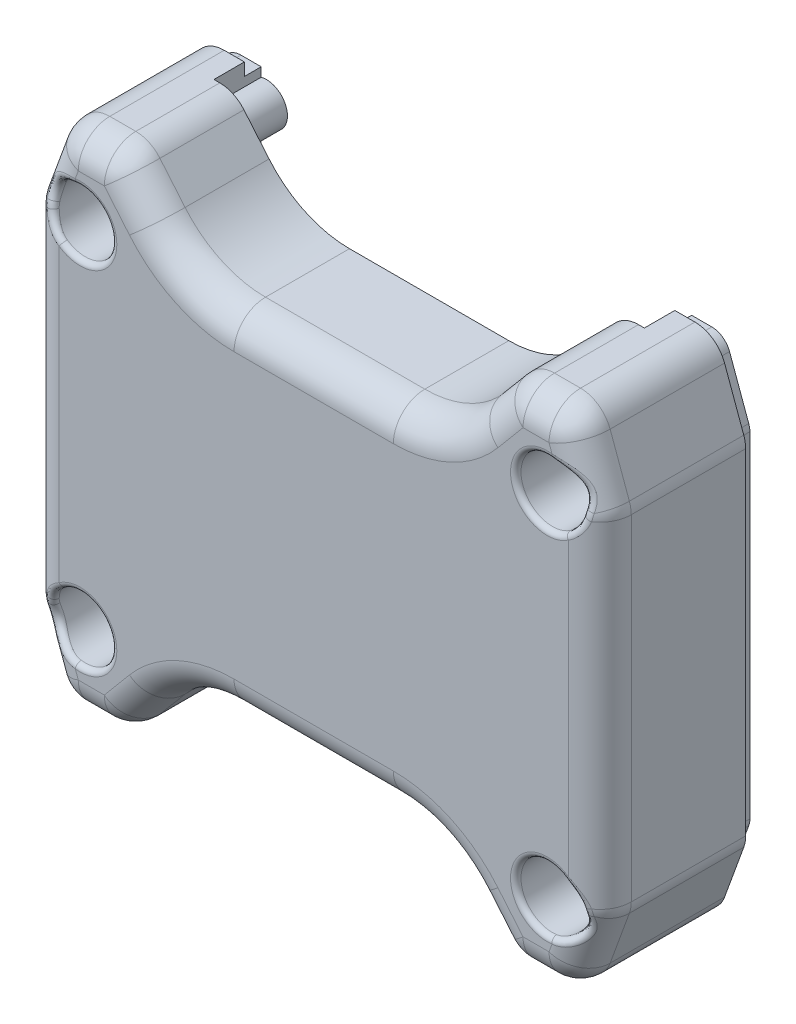
SolidWorks part; units mm, degrees
ref_plane "Alzado" through (0, 0, 0) normal (0, 0, 1) x (1, 0, 0)
ref_plane "Planta" through (0, 0, 0) normal (0, 1, 0) x (1, 0, 0)
ref_plane "Vista lateral" through (0, 0, 0) normal (1, 0, 0) x (0, 0, -1)
sketch "Croquis2" plane through (0, 0, 0) normal (0, 0, 1) x (1, 0, 0)
  line L0 (-20, 7.75) -> (-20, 15.75)
  line L1 (-20, -41.25) -> (20, -41.25)
  line L2 (-20, -41.25) -> (-20, -24.25)
  line L3 (-20, 38.75) -> (20, 38.75)
  line L4 (20, -41.25) -> (20, -24.25)
  line L5 (-20, 7.75) -> (5, 7.75)
  line L6 (-20, 4.75) -> (5, 4.75)
  line L7 (5, 7.75) -> (5, 4.75)
  line L8 (20, -10.25) -> (-5, -10.25)
  line L9 (20, -7.25) -> (-5, -7.25)
  line L10 (-5, -10.25) -> (-5, -7.25)
  line L11 (20, -7.25) -> (20, 15.75)
  line L12 (0, 38.75) -> (0, -41.25) construction
  line L14 (-20, 21.75) -> (-20, 38.75)
  line L15 (20, 21.75) -> (20, 38.75)
  line L16 (-20, -21.25) -> (20, -21.25) construction
  line L17 (-20, -18.25) -> (-20, 4.75)
  line L18 (20, -18.25) -> (20, -10.25)
  line L19 (0, 15.25) -> (0, -17.75) construction
  line L24 (27.25, -1.25) -> (-27.25, -1.25) construction
  line L29 (0, 15.25) -> (0, -17.75) construction
  line L39 (22.4196, 22.75) -> (21, 22.75)
  line L40 (21, 22.75) -> (21, 21.75)
  line L41 (21, 21.75) -> (22.4196, 21.75)
  line L42 (24.299, 20.434) -> (26.25, 15.0737)
  line L43 (26.25, 15.0737) -> (26.25, -17.5737)
  line L44 (26.25, -17.5737) -> (24.299, -22.934)
  line L45 (22.4196, -24.25) -> (21, -24.25)
  line L46 (21, -24.25) -> (21, -25.25)
  line L47 (21, -25.25) -> (22.4196, -25.25)
  line L48 (25.2387, -23.2761) -> (27.0691, -18.2471)
  line L49 (27.25, -17.221) -> (27.25, 14.721)
  line L50 (27.0691, 15.7471) -> (25.2387, 20.7761)
  line L51 (-22.4196, -25.25) -> (-21, -25.25)
  line L52 (-21, -25.25) -> (-21, -24.25)
  line L53 (-21, -24.25) -> (-22.4196, -24.25)
  line L54 (-24.299, -22.934) -> (-26.25, -17.5737)
  line L55 (-26.25, -17.5737) -> (-26.25, 15.0737)
  line L56 (-26.25, 15.0737) -> (-24.299, 20.434)
  line L57 (-22.4196, 21.75) -> (-21, 21.75)
  line L58 (-21, 21.75) -> (-21, 22.75)
  line L59 (-21, 22.75) -> (-22.4196, 22.75)
  line L60 (-25.2387, 20.7761) -> (-27.0691, 15.7471)
  line L61 (-27.25, 14.721) -> (-27.25, -17.221)
  line L62 (-27.0691, -18.2471) -> (-25.2387, -23.2761)
  line L63 (-21, 22.75) -> (-21, 21.75)
  line L64 (-21, 21.75) -> (-22.4196, 21.75)
  line L65 (-24.299, 20.434) -> (-26.25, 15.0737)
  line L66 (-26.25, 15.0737) -> (-26.25, -17.5737)
  line L67 (-26.25, -17.5737) -> (-24.299, -22.934)
  line L68 (-22.4196, -24.25) -> (-21, -24.25)
  line L69 (-21, -24.25) -> (-21, -25.25)
  line L70 (-21, -25.25) -> (-19.9422, -25.25)
  line L71 (-17.644, -24.1784) -> (-15.2474, -21.3221)
  line L72 (-7.5869, -17.75) -> (7.5869, -17.75)
  line L73 (15.2474, -21.3221) -> (17.644, -24.1784)
  line L74 (19.9422, -25.25) -> (21, -25.25)
  line L75 (21, -25.25) -> (21, -24.25)
  line L76 (21, -24.25) -> (22.4196, -24.25)
  line L77 (24.299, -22.934) -> (26.25, -17.5737)
  line L78 (26.25, -17.5737) -> (26.25, 15.0737)
  line L79 (26.25, 15.0737) -> (24.299, 20.434)
  line L80 (22.4196, 21.75) -> (21, 21.75)
  line L81 (21, 21.75) -> (21, 22.75)
  line L82 (21, 22.75) -> (19.9422, 22.75)
  line L83 (17.644, 21.6784) -> (15.2474, 18.8221)
  line L84 (7.5869, 15.25) -> (-7.5869, 15.25)
  line L85 (-15.2474, 18.8221) -> (-17.644, 21.6784)
  line L86 (-19.9422, 22.75) -> (-21, 22.75)
  line L87 (-20, -41.25) -> (20, -41.25)
  line L88 (-20, -41.25) -> (-20, -24.25)
  line L89 (-5, -10.25) -> (-5, -7.25)
  line L90 (20, -7.25) -> (-5, -7.25)
  line L91 (20, -10.25) -> (-5, -10.25)
  line L92 (5, 7.75) -> (5, 4.75)
  line L93 (-20, 4.75) -> (5, 4.75)
  line L94 (-20, 7.75) -> (5, 7.75)
  line L95 (-20, 7.75) -> (-20, 15.75)
  line L96 (20, -7.25) -> (20, 15.75)
  line L97 (20, -18.25) -> (20, -10.25)
  line L98 (20, -41.25) -> (20, -24.25)
  line L99 (-20, -18.25) -> (-20, 4.75)
  line L100 (-20, 21.75) -> (-20, 38.75)
  line L101 (-20, 38.75) -> (20, 38.75)
  line L102 (20, 21.75) -> (20, 38.75)
  line L103 (-27.0691, -18.2471) -> (-25.2387, -23.2761)
  line L104 (-27.25, 14.721) -> (-27.25, -17.221)
  line L105 (-25.2387, 20.7761) -> (-27.0691, 15.7471)
  line L106 (-21, 21.75) -> (-22.4196, 21.75)
  line L107 (-22.4196, -24.25) -> (-21, -24.25)
  line L108 (-21, -24.25) -> (-21, -25.25)
  line L109 (-21, 22.75) -> (-21, 21.75)
  line L110 (-26.25, 15.0737) -> (-26.25, -17.5737)
  line L111 (-24.299, 20.434) -> (-26.25, 15.0737)
  line L112 (-19.9422, 22.75) -> (-22.4196, 22.75)
  line L113 (-22.4196, -25.25) -> (-19.9422, -25.25)
  line L114 (-26.25, -17.5737) -> (-24.299, -22.934)
  line L115 (27.0691, 15.7471) -> (25.2387, 20.7761)
  line L116 (27.25, -17.221) -> (27.25, 14.721)
  line L117 (25.2387, -23.2761) -> (27.0691, -18.2471)
  line L118 (21, -24.25) -> (22.4196, -24.25)
  line L119 (26.25, 15.0737) -> (24.299, 20.434)
  line L120 (22.4196, 21.75) -> (21, 21.75)
  line L121 (21, 21.75) -> (21, 22.75)
  line L122 (21, -25.25) -> (21, -24.25)
  line L123 (22.4196, 22.75) -> (19.9422, 22.75)
  line L124 (26.25, -17.5737) -> (26.25, 15.0737)
  line L125 (24.299, -22.934) -> (26.25, -17.5737)
  line L126 (19.9422, -25.25) -> (22.4196, -25.25)
  line L127 (-17.644, 21.6784) -> (-15.2474, 18.8221)
  line L128 (7.5869, 15.25) -> (-7.5869, 15.25)
  line L129 (15.2474, 18.8221) -> (17.644, 21.6784)
  line L130 (17.644, -24.1784) -> (15.2474, -21.3221)
  line L131 (-7.5869, -17.75) -> (7.5869, -17.75)
  line L132 (-15.2474, -21.3221) -> (-17.644, -24.1784)
  line L133 (-25.25, 13.75) -> (-24.6867, 13.75)
  line L134 (19.8133, -16.25) -> (-19.8133, -16.25)
  line L135 (-19.8133, 13.75) -> (19.8133, 13.75)
  line L136 (24.6867, 13.75) -> (25.25, 13.75)
  line L137 (25.25, -16.25) -> (24.6867, -16.25)
  line L138 (-25.25, -16.25) -> (-25.25, 13.75)
  line L139 (-24.6867, -16.25) -> (-25.25, -16.25)
  line L140 (25.25, 13.75) -> (25.25, -16.25)
  line L141 (-25.25, -14) -> (-17.25, -14)
  line L142 (-17.25, -13) -> (-17.25, -16)
  line L143 (-17.25, -16) -> (-20.0139, -16)
  line L144 (-24.4861, -16) -> (-25.25, -16)
  line L145 (20.0139, -16) -> (17.25, -16)
  line L146 (17.25, -14) -> (25.25, -14)
  line L147 (17.25, -16) -> (17.25, -14)
  line L148 (25.25, -16) -> (24.4861, -16)
  line L149 (25.25, 11.5) -> (17.25, 11.5)
  line L150 (17.25, 13.5) -> (20.0139, 13.5)
  line L151 (17.25, 11.5) -> (17.25, 13.5)
  line L152 (24.4861, 13.5) -> (25.25, 13.5)
  line L153 (-17.25, 13.5) -> (-17.25, 10.5)
  line L154 (-20.0139, 13.5) -> (-17.25, 13.5)
  line L155 (-25.25, 13.5) -> (-24.4861, 13.5)
  line L156 (-17.25, 11.5) -> (-25.25, 11.5)
  line L157 (-24.25, 10.5) -> (-24.25, 6.5)
  line L158 (-24.25, 6.5) -> (-25.25, 6.5)
  line L159 (-17.25, 10.5) -> (-24.25, 10.5)
  line L160 (19.75, -13) -> (19.75, -14)
  line L161 (24.25, -13) -> (24.25, -9)
  line L162 (25.25, -9) -> (24.25, -9)
  line L163 (19.75, -13) -> (24.25, -13)
  line L164 (-24.25, -9) -> (-24.25, -13)
  line L165 (-24.25, -13) -> (-17.25, -13)
  line L166 (-25.25, -9) -> (-24.25, -9)
  line L167 (24.9375, 0.5) -> (24.9375, 2.5)
  line L168 (16, 13.75) -> (16, -16.25)
  line L169 (24.9375, 2.5) -> (25.25, 2.5)
  line L170 (-16, -16.25) -> (-16, 13.75)
  line L171 (24.9375, 0.5) -> (21.25, 0.5)
  line L172 (21.25, 0.5) -> (21.25, 11.5)
  line L173 (13.5, -11.25) -> (13.5, -6.25)
  line L174 (13.5, -6.25) -> (15.5, -6.25)
  line L175 (15.5, -6.25) -> (15.5, -13.25)
  line L176 (15.5, -13.25) -> (8, -13.25)
  line L177 (8, -13.25) -> (8, -11.25)
  line L178 (8, -11.25) -> (13.5, -11.25)
  line L179 (-13.5, 3.25) -> (-15.5, 3.25)
  line L180 (-15.5, 3.25) -> (-15.5, 10.25)
  line L181 (-15.5, 10.25) -> (-8, 10.25)
  line L182 (-8, 10.25) -> (-8, 8.25)
  line L183 (-8, 8.25) -> (-13.5, 8.25)
  line L184 (-13.5, 8.25) -> (-13.5, 3.25)
  line L185 (-13.5, -11.25) -> (-8, -11.25)
  line L186 (-8, -11.25) -> (-8, -13.25)
  line L187 (-8, -13.25) -> (-15.5, -13.25)
  line L188 (-15.5, -13.25) -> (-15.5, -6.25)
  line L189 (-15.5, -6.25) -> (-13.5, -6.25)
  line L190 (-13.5, -6.25) -> (-13.5, -11.25)
  line L191 (8, 10.25) -> (15.5, 10.25)
  line L192 (13.5, 3.25) -> (13.5, 8.25)
  line L193 (13.5, 8.25) -> (8, 8.25)
  line L194 (8, 8.25) -> (8, 10.25)
  line L195 (15.5, 10.25) -> (15.5, 3.25)
  line L196 (15.5, 3.25) -> (13.5, 3.25)
  line L197 (-12.5, -3.75) -> (-12.5, 4.625)
  line L198 (10.5, -5.75) -> (-10.5, -5.75)
  line L199 (12.5, 4.625) -> (12.5, -3.75)
  line L200 (-10.5, 6.625) -> (10.5, 6.625)
  circle A0 centre (0, 24.75) radius 8
  circle A1 centre (0, -27.25) radius 8
  arc A2 (-20, 15.75) -> (-20, 21.75) centre (-20, 18.75) ccw
  arc A3 (20, 21.75) -> (20, 15.75) centre (20, 18.75) ccw
  arc A4 (-20, -24.25) -> (-20, -18.25) centre (-20, -21.25) ccw
  arc A5 (20, -18.25) -> (20, -24.25) centre (20, -21.25) ccw
  circle A6 centre (-20, 18.75) radius 2
  circle A7 centre (20, 18.75) radius 2
  circle A8 centre (20, -21.25) radius 2
  circle A9 centre (-20, -21.25) radius 2
  circle A10 centre (-22.25, -18) radius 1.5
  circle A11 centre (-22.25, -18) radius 3
  circle A12 centre (20, -21.25) radius 2
  circle A13 centre (22.25, -18) radius 1.5
  circle A14 centre (22.25, -18) radius 3
  circle A15 centre (22.25, 15.5) radius 3
  circle A16 centre (22.25, 15.5) radius 1.5
  circle A17 centre (-22.25, 15.5) radius 3
  circle A18 centre (-22.25, 15.5) radius 1.5
  arc A19 (24.299, 20.434) -> (22.4196, 21.75) centre (22.4196, 19.75) ccw
  arc A20 (22.4196, -24.25) -> (24.299, -22.934) centre (22.4196, -22.25) ccw
  arc A21 (22.4196, -25.25) -> (25.2387, -23.2761) centre (22.4196, -22.25) ccw
  arc A22 (27.0691, -18.2471) -> (27.25, -17.221) centre (24.25, -17.221) ccw
  arc A23 (27.25, 14.721) -> (27.0691, 15.7471) centre (24.25, 14.721) ccw
  arc A24 (25.2387, 20.7761) -> (22.4196, 22.75) centre (22.4196, 19.75) ccw
  arc A25 (-24.299, -22.934) -> (-22.4196, -24.25) centre (-22.4196, -22.25) ccw
  arc A26 (-22.4196, 21.75) -> (-24.299, 20.434) centre (-22.4196, 19.75) ccw
  arc A27 (-22.4196, 22.75) -> (-25.2387, 20.7761) centre (-22.4196, 19.75) ccw
  arc A28 (-27.0691, 15.7471) -> (-27.25, 14.721) centre (-24.25, 14.721) ccw
  arc A29 (-27.25, -17.221) -> (-27.0691, -18.2471) centre (-24.25, -17.221) ccw
  arc A30 (-25.2387, -23.2761) -> (-22.4196, -25.25) centre (-22.4196, -22.25) ccw
  arc A31 (-22.4196, 21.75) -> (-24.299, 20.434) centre (-22.4196, 19.75) ccw
  arc A32 (-24.299, -22.934) -> (-22.4196, -24.25) centre (-22.4196, -22.25) ccw
  arc A33 (-19.9422, -25.25) -> (-17.644, -24.1784) centre (-19.9422, -22.25) ccw
  arc A34 (-7.5869, -17.75) -> (-15.2474, -21.3221) centre (-7.5869, -27.75) ccw
  arc A35 (15.2474, -21.3221) -> (7.5869, -17.75) centre (7.5869, -27.75) ccw
  arc A36 (17.644, -24.1784) -> (19.9422, -25.25) centre (19.9422, -22.25) ccw
  arc A37 (22.4196, -24.25) -> (24.299, -22.934) centre (22.4196, -22.25) ccw
  arc A38 (24.299, 20.434) -> (22.4196, 21.75) centre (22.4196, 19.75) ccw
  arc A39 (19.9422, 22.75) -> (17.644, 21.6784) centre (19.9422, 19.75) ccw
  arc A40 (7.5869, 15.25) -> (15.2474, 18.8221) centre (7.5869, 25.25) ccw
  arc A41 (-15.2474, 18.8221) -> (-7.5869, 15.25) centre (-7.5869, 25.25) ccw
  arc A42 (-17.644, 21.6784) -> (-19.9422, 22.75) centre (-19.9422, 19.75) ccw
  circle A43 centre (0, -27.25) radius 8
  circle A44 centre (0, 24.75) radius 8
  arc A45 (-20, 15.75) -> (-20, 21.75) centre (-20, 18.75) ccw
  arc A46 (20, -18.25) -> (20, -24.25) centre (20, -21.25) ccw
  arc A47 (-20, -24.25) -> (-20, -18.25) centre (-20, -21.25) ccw
  arc A48 (20, 21.75) -> (20, 15.75) centre (20, 18.75) ccw
  circle A49 centre (-20, -21.25) radius 2
  circle A50 centre (20, -21.25) radius 2
  circle A51 centre (20, 18.75) radius 2
  circle A52 centre (-20, 18.75) radius 2
  circle A53 centre (22.25, 15.5) radius 1.5
  circle A54 centre (22.25, -18) radius 1.5
  circle A55 centre (-22.25, -18) radius 1.5
  circle A56 centre (-22.25, 15.5) radius 1.5
  arc A57 (-22.4196, 22.75) -> (-25.2387, 20.7761) centre (-22.4196, 19.75) ccw
  arc A58 (-24.299, -22.934) -> (-22.4196, -24.25) centre (-22.4196, -22.25) ccw
  arc A59 (-27.25, -17.221) -> (-27.0691, -18.2471) centre (-24.25, -17.221) ccw
  arc A60 (-25.2387, -23.2761) -> (-22.4196, -25.25) centre (-22.4196, -22.25) ccw
  arc A61 (-27.0691, 15.7471) -> (-27.25, 14.721) centre (-24.25, 14.721) ccw
  arc A62 (-22.4196, 21.75) -> (-24.299, 20.434) centre (-22.4196, 19.75) ccw
  arc A63 (27.25, 14.721) -> (27.0691, 15.7471) centre (24.25, 14.721) ccw
  arc A64 (27.0691, -18.2471) -> (27.25, -17.221) centre (24.25, -17.221) ccw
  arc A65 (22.4196, -24.25) -> (24.299, -22.934) centre (22.4196, -22.25) ccw
  arc A66 (24.299, 20.434) -> (22.4196, 21.75) centre (22.4196, 19.75) ccw
  arc A67 (25.2387, 20.7761) -> (22.4196, 22.75) centre (22.4196, 19.75) ccw
  arc A68 (22.4196, -25.25) -> (25.2387, -23.2761) centre (22.4196, -22.25) ccw
  arc A69 (-17.644, 21.6784) -> (-19.9422, 22.75) centre (-19.9422, 19.75) ccw
  arc A70 (-15.2474, 18.8221) -> (-7.5869, 15.25) centre (-7.5869, 25.25) ccw
  arc A71 (7.5869, 15.25) -> (15.2474, 18.8221) centre (7.5869, 25.25) ccw
  arc A72 (19.9422, 22.75) -> (17.644, 21.6784) centre (19.9422, 19.75) ccw
  arc A73 (17.644, -24.1784) -> (19.9422, -25.25) centre (19.9422, -22.25) ccw
  arc A74 (15.2474, -21.3221) -> (7.5869, -17.75) centre (7.5869, -27.75) ccw
  arc A75 (-7.5869, -17.75) -> (-15.2474, -21.3221) centre (-7.5869, -27.75) ccw
  arc A76 (-19.9422, -25.25) -> (-17.644, -24.1784) centre (-19.9422, -22.25) ccw
  arc A77 (-19.8133, -16.25) -> (-24.6867, -16.25) centre (-22.25, -18) ccw
  arc A78 (24.6867, -16.25) -> (19.8133, -16.25) centre (22.25, -18) ccw
  arc A79 (19.8133, 13.75) -> (24.6867, 13.75) centre (22.25, 15.5) ccw
  arc A80 (-24.6867, 13.75) -> (-19.8133, 13.75) centre (-22.25, 15.5) ccw
  arc A81 (-10.5, 6.625) -> (-12.5, 4.625) centre (-10.5, 4.625) ccw
  arc A82 (-12.5, -3.75) -> (-10.5, -5.75) centre (-10.5, -3.75) ccw
  arc A83 (10.5, -5.75) -> (12.5, -3.75) centre (10.5, -3.75) ccw
  arc A84 (12.5, 4.625) -> (10.5, 6.625) centre (10.5, 4.625) ccw
  point P146 (0, -1.25)
sketch "Croquis3" plane through (0, 0, 0) normal (0, 0, 1) x (1, 0, 0)
  line L0 (15.2474, -21.3221) -> (17.644, -24.1784) construction
  line L1 (-21, 22.75) -> (-22.4196, 22.75) construction
  line L2 (-25.2387, 20.7761) -> (-27.0691, 15.7471) construction
  line L3 (-27.25, 14.721) -> (-27.25, -17.221) construction
  line L4 (-27.0691, -18.2471) -> (-25.2387, -23.2761) construction
  line L5 (-22.4196, -25.25) -> (-21, -25.25) construction
  line L6 (-21, -25.25) -> (-19.9422, -25.25) construction
  line L7 (-17.644, -24.1784) -> (-15.2474, -21.3221) construction
  line L8 (-7.5869, -17.75) -> (7.5869, -17.75) construction
  line L9 (22.4196, 22.75) -> (21, 22.75) construction
  line L10 (-21, -25.25) -> (-19.9422, -25.25)
  line L11 (-19.9422, 22.75) -> (-21, 22.75) construction
  line L12 (-15.2474, 18.8221) -> (-17.644, 21.6784) construction
  line L13 (7.5869, 15.25) -> (-7.5869, 15.25) construction
  line L14 (17.644, 21.6784) -> (15.2474, 18.8221) construction
  line L15 (21, 22.75) -> (19.9422, 22.75) construction
  line L16 (27.0691, 15.7471) -> (25.2387, 20.7761) construction
  line L17 (19.9422, -25.25) -> (21, -25.25) construction
  line L18 (21, -25.25) -> (22.4196, -25.25) construction
  line L19 (25.2387, -23.2761) -> (27.0691, -18.2471) construction
  line L20 (27.25, -17.221) -> (27.25, 14.721) construction
  line L21 (19.9422, -25.25) -> (21, -25.25)
  line L22 (21, -25.25) -> (22.4196, -25.25)
  line L23 (25.2387, -23.2761) -> (27.0691, -18.2471)
  line L24 (27.25, -17.221) -> (27.25, 14.721)
  line L25 (27.0691, 15.7471) -> (25.2387, 20.7761)
  line L26 (22.4196, 22.75) -> (21, 22.75)
  line L27 (21, 22.75) -> (19.9422, 22.75)
  line L28 (17.644, 21.6784) -> (15.2474, 18.8221)
  line L29 (7.5869, 15.25) -> (-7.5869, 15.25)
  line L30 (-15.2474, 18.8221) -> (-17.644, 21.6784)
  line L31 (-19.9422, 22.75) -> (-21, 22.75)
  line L32 (-21, 22.75) -> (-22.4196, 22.75)
  line L33 (-25.2387, 20.7761) -> (-27.0691, 15.7471)
  line L34 (-27.25, 14.721) -> (-27.25, -17.221)
  line L35 (-27.0691, -18.2471) -> (-25.2387, -23.2761)
  line L36 (21.25, 0.5) -> (21.25, 11.5) construction
  line L37 (-22.4196, -25.25) -> (-21, -25.25)
  line L38 (-17.644, -24.1784) -> (-15.2474, -21.3221)
  line L39 (-7.5869, -17.75) -> (7.5869, -17.75)
  line L40 (15.2474, -21.3221) -> (17.644, -24.1784)
  line L41 (-24.25, -14.75) -> (21.25, -14.75)
  line L42 (-24.25, -14.75) -> (-24.25, 12.25)
  line L43 (-24.25, 12.25) -> (21.25, 12.25)
  line L44 (21.25, -14.75) -> (21.25, 12.25)
  arc A0 (-22.4196, 22.75) -> (-25.2387, 20.7761) centre (-22.4196, 19.75) ccw construction
  arc A1 (-27.0691, 15.7471) -> (-27.25, 14.721) centre (-24.25, 14.721) ccw construction
  arc A2 (-27.25, -17.221) -> (-27.0691, -18.2471) centre (-24.25, -17.221) ccw construction
  arc A3 (-25.2387, -23.2761) -> (-22.4196, -25.25) centre (-22.4196, -22.25) ccw construction
  arc A4 (-19.9422, -25.25) -> (-17.644, -24.1784) centre (-19.9422, -22.25) ccw construction
  arc A5 (-7.5869, -17.75) -> (-15.2474, -21.3221) centre (-7.5869, -27.75) ccw construction
  arc A6 (15.2474, -21.3221) -> (7.5869, -17.75) centre (7.5869, -27.75) ccw construction
  arc A7 (17.644, -24.1784) -> (19.9422, -25.25) centre (19.9422, -22.25) ccw construction
  arc A8 (-17.644, 21.6784) -> (-19.9422, 22.75) centre (-19.9422, 19.75) ccw construction
  arc A9 (-15.2474, 18.8221) -> (-7.5869, 15.25) centre (-7.5869, 25.25) ccw construction
  arc A10 (7.5869, 15.25) -> (15.2474, 18.8221) centre (7.5869, 25.25) ccw construction
  arc A11 (19.9422, 22.75) -> (17.644, 21.6784) centre (19.9422, 19.75) ccw construction
  arc A12 (25.2387, 20.7761) -> (22.4196, 22.75) centre (22.4196, 19.75) ccw construction
  arc A13 (22.4196, -25.25) -> (25.2387, -23.2761) centre (22.4196, -22.25) ccw construction
  arc A14 (27.0691, -18.2471) -> (27.25, -17.221) centre (24.25, -17.221) ccw construction
  arc A15 (27.25, 14.721) -> (27.0691, 15.7471) centre (24.25, 14.721) ccw construction
  arc A16 (22.4196, -25.25) -> (25.2387, -23.2761) centre (22.4196, -22.25) ccw
  arc A17 (27.0691, -18.2471) -> (27.25, -17.221) centre (24.25, -17.221) ccw
  arc A18 (27.25, 14.721) -> (27.0691, 15.7471) centre (24.25, 14.721) ccw
  arc A19 (25.2387, 20.7761) -> (22.4196, 22.75) centre (22.4196, 19.75) ccw
  arc A20 (19.9422, 22.75) -> (17.644, 21.6784) centre (19.9422, 19.75) ccw
  arc A21 (7.5869, 15.25) -> (15.2474, 18.8221) centre (7.5869, 25.25) ccw
  arc A22 (-15.2474, 18.8221) -> (-7.5869, 15.25) centre (-7.5869, 25.25) ccw
  arc A23 (-17.644, 21.6784) -> (-19.9422, 22.75) centre (-19.9422, 19.75) ccw
  arc A24 (-22.4196, 22.75) -> (-25.2387, 20.7761) centre (-22.4196, 19.75) ccw
  arc A25 (-27.0691, 15.7471) -> (-27.25, 14.721) centre (-24.25, 14.721) ccw
  arc A26 (-27.25, -17.221) -> (-27.0691, -18.2471) centre (-24.25, -17.221) ccw
  arc A27 (-25.2387, -23.2761) -> (-22.4196, -25.25) centre (-22.4196, -22.25) ccw
  arc A28 (-19.9422, -25.25) -> (-17.644, -24.1784) centre (-19.9422, -22.25) ccw
  arc A29 (-7.5869, -17.75) -> (-15.2474, -21.3221) centre (-7.5869, -27.75) ccw
  arc A30 (15.2474, -21.3221) -> (7.5869, -17.75) centre (7.5869, -27.75) ccw
  arc A31 (17.644, -24.1784) -> (19.9422, -25.25) centre (19.9422, -22.25) ccw
  dimension "D1" = 3
  dimension "D2" = 3
  dimension "D3" = 6
  dimension "D4" = 3
extrude "Saliente-Extruir1" add sketch "Croquis3" along normal blind 9
sketch "Croquis4" plane through (0, 0, 9) normal (0, 0, 1) x (1, 0, 0)
  line L16 (19.9422, -25.25) -> (22.4196, -25.25)
  line L17 (25.2387, -23.2761) -> (27.0691, -18.2471)
  line L18 (27.25, -17.221) -> (27.25, 14.721)
  line L19 (27.0691, 15.7471) -> (25.2387, 20.7761)
  line L20 (22.4196, 22.75) -> (19.9422, 22.75)
  line L21 (17.644, 21.6784) -> (15.2474, 18.8221)
  line L22 (7.5869, 15.25) -> (-7.5869, 15.25)
  line L23 (-15.2474, 18.8221) -> (-17.644, 21.6784)
  line L24 (-19.9422, 22.75) -> (-22.4196, 22.75)
  line L25 (-25.2387, 20.7761) -> (-27.0691, 15.7471)
  line L26 (-27.25, 14.721) -> (-27.25, -17.221)
  line L27 (-27.0691, -18.2471) -> (-25.2387, -23.2761)
  line L28 (-22.4196, -25.25) -> (-19.9422, -25.25)
  line L29 (-17.644, -24.1784) -> (-15.2474, -21.3221)
  line L30 (-7.5869, -17.75) -> (7.5869, -17.75)
  line L31 (15.2474, -21.3221) -> (17.644, -24.1784)
  line L32 (19.9422, -25.25) -> (22.4196, -25.25)
  line L33 (25.2387, -23.2761) -> (27.0691, -18.2471)
  line L34 (27.25, -17.221) -> (27.25, 14.721)
  line L35 (27.0691, 15.7471) -> (25.2387, 20.7761)
  line L36 (22.4196, 22.75) -> (19.9422, 22.75)
  line L37 (17.644, 21.6784) -> (15.2474, 18.8221)
  line L38 (7.5869, 15.25) -> (-7.5869, 15.25)
  line L39 (-15.2474, 18.8221) -> (-17.644, 21.6784)
  line L40 (-19.9422, 22.75) -> (-22.4196, 22.75)
  line L41 (-25.2387, 20.7761) -> (-27.0691, 15.7471)
  line L42 (-27.25, 14.721) -> (-27.25, -17.221)
  line L43 (-27.0691, -18.2471) -> (-25.2387, -23.2761)
  line L44 (-22.4196, -25.25) -> (-19.9422, -25.25)
  line L45 (-17.644, -24.1784) -> (-15.2474, -21.3221)
  line L46 (-7.5869, -17.75) -> (7.5869, -17.75)
  line L47 (15.2474, -21.3221) -> (17.644, -24.1784)
  arc A16 (17.644, -24.1784) -> (19.9422, -25.25) centre (19.9422, -22.25) ccw
  arc A17 (22.4196, -25.25) -> (25.2387, -23.2761) centre (22.4196, -22.25) ccw
  arc A18 (27.0691, -18.2471) -> (27.25, -17.221) centre (24.25, -17.221) ccw
  arc A19 (27.25, 14.721) -> (27.0691, 15.7471) centre (24.25, 14.721) ccw
  arc A20 (25.2387, 20.7761) -> (22.4196, 22.75) centre (22.4196, 19.75) ccw
  arc A21 (19.9422, 22.75) -> (17.644, 21.6784) centre (19.9422, 19.75) ccw
  arc A22 (7.5869, 15.25) -> (15.2474, 18.8221) centre (7.5869, 25.25) ccw
  arc A23 (-15.2474, 18.8221) -> (-7.5869, 15.25) centre (-7.5869, 25.25) ccw
  arc A24 (-17.644, 21.6784) -> (-19.9422, 22.75) centre (-19.9422, 19.75) ccw
  arc A25 (-22.4196, 22.75) -> (-25.2387, 20.7761) centre (-22.4196, 19.75) ccw
  arc A26 (-27.0691, 15.7471) -> (-27.25, 14.721) centre (-24.25, 14.721) ccw
  arc A27 (-27.25, -17.221) -> (-27.0691, -18.2471) centre (-24.25, -17.221) ccw
  arc A28 (-25.2387, -23.2761) -> (-22.4196, -25.25) centre (-22.4196, -22.25) ccw
  arc A29 (-19.9422, -25.25) -> (-17.644, -24.1784) centre (-19.9422, -22.25) ccw
  arc A30 (-7.5869, -17.75) -> (-15.2474, -21.3221) centre (-7.5869, -27.75) ccw
  arc A31 (15.2474, -21.3221) -> (7.5869, -17.75) centre (7.5869, -27.75) ccw
  arc A32 (17.644, -24.1784) -> (19.9422, -25.25) centre (19.9422, -22.25) ccw
  arc A33 (22.4196, -25.25) -> (25.2387, -23.2761) centre (22.4196, -22.25) ccw
  arc A34 (27.0691, -18.2471) -> (27.25, -17.221) centre (24.25, -17.221) ccw
  arc A35 (27.25, 14.721) -> (27.0691, 15.7471) centre (24.25, 14.721) ccw
  arc A36 (25.2387, 20.7761) -> (22.4196, 22.75) centre (22.4196, 19.75) ccw
  arc A37 (19.9422, 22.75) -> (17.644, 21.6784) centre (19.9422, 19.75) ccw
  arc A38 (7.5869, 15.25) -> (15.2474, 18.8221) centre (7.5869, 25.25) ccw
  arc A39 (-15.2474, 18.8221) -> (-7.5869, 15.25) centre (-7.5869, 25.25) ccw
  arc A40 (-17.644, 21.6784) -> (-19.9422, 22.75) centre (-19.9422, 19.75) ccw
  arc A41 (-22.4196, 22.75) -> (-25.2387, 20.7761) centre (-22.4196, 19.75) ccw
  arc A42 (-27.0691, 15.7471) -> (-27.25, 14.721) centre (-24.25, 14.721) ccw
  arc A43 (-27.25, -17.221) -> (-27.0691, -18.2471) centre (-24.25, -17.221) ccw
  arc A44 (-25.2387, -23.2761) -> (-22.4196, -25.25) centre (-22.4196, -22.25) ccw
  arc A45 (-19.9422, -25.25) -> (-17.644, -24.1784) centre (-19.9422, -22.25) ccw
  arc A46 (-7.5869, -17.75) -> (-15.2474, -21.3221) centre (-7.5869, -27.75) ccw
  arc A47 (15.2474, -21.3221) -> (7.5869, -17.75) centre (7.5869, -27.75) ccw
  dimension "D1" = 0
extrude "Saliente-Extruir2" add sketch "Croquis4" along normal blind 2
sketch "Croquis5" plane through (0, 0, 0) normal (0, 0, -1) x (-1, 0, 0)
  circle A0 centre (-20, -21.25) radius 2 construction
  circle A1 centre (20, -21.25) radius 2 construction
  circle A2 centre (20, 18.75) radius 2 construction
  circle A3 centre (-20, 18.75) radius 2 construction
  circle A4 centre (-20, -21.25) radius 2 construction
  circle A5 centre (20, -21.25) radius 2 construction
  circle A6 centre (20, 18.75) radius 2
  circle A7 centre (-20, 18.75) radius 2
  circle A8 centre (-20, -21.25) radius 2.5
  circle A9 centre (20, -21.25) radius 2.5
  dimension "D1" = 5
  dimension "D2" = 5
extrude "Saliente-Extruir3" add sketch "Croquis5" along normal blind 4.5
sketch "Croquis6" plane through (0, 0, 0) normal (0, 0, -1) x (-1, 0, 0)
  line L0 (-20, -25.25) -> (-20, -23.25)
  line L1 (-20, -41.25) -> (-20, -24.25) construction
  line L2 (20, -41.25) -> (20, -24.25) construction
  line L3 (20, -25.25) -> (20, -23.25)
  line L4 (-20.5, 16.8135) -> (-20.5, 12.25)
  line L5 (20.5, 16.8135) -> (20.5, 12.25)
  line L6 (-20.5, 22.75) -> (-20.5, 20.6865)
  line L7 (20.5, 22.75) -> (20.5, 20.6865)
  line L8 (-20, 21.75) -> (-20, 38.75) construction
  line L9 (20, 21.75) -> (20, 38.75) construction
  line L10 (-21.25, -14.75) -> (-21.25, 12.25) construction
  line L11 (24.25, -14.75) -> (-21.25, -14.75) construction
  line L12 (24.25, 12.25) -> (24.25, -14.75) construction
  line L13 (-21.25, 12.25) -> (24.25, 12.25) construction
  line L14 (24.25, -14.75) -> (20, -14.75)
  line L15 (24.25, 12.25) -> (24.25, -14.75)
  line L16 (-17.644, -24.1784) -> (-15.2474, -21.3221)
  line L17 (-7.5869, -17.75) -> (7.5869, -17.75)
  line L18 (15.2474, -21.3221) -> (17.644, -24.1784)
  line L19 (19.9422, -25.25) -> (22.4196, -25.25)
  line L20 (25.2387, -23.2761) -> (27.0691, -18.2471)
  line L21 (27.25, -17.221) -> (27.25, 14.721)
  line L22 (27.0691, 15.7471) -> (25.2387, 20.7761)
  line L23 (22.4196, 22.75) -> (19.9422, 22.75)
  line L24 (17.644, 21.6784) -> (15.2474, 18.8221)
  line L25 (7.5869, 15.25) -> (-7.5869, 15.25)
  line L26 (-15.2474, 18.8221) -> (-17.644, 21.6784)
  line L27 (-19.9422, 22.75) -> (-22.4196, 22.75)
  line L28 (-25.2387, 20.7761) -> (-27.0691, 15.7471)
  line L29 (-27.25, 14.721) -> (-27.25, -17.221)
  line L30 (-27.0691, -18.2471) -> (-25.2387, -23.2761)
  line L31 (-22.4196, -25.25) -> (-19.9422, -25.25)
  line L35 (20, -25.25) -> (22.4196, -25.25)
  line L36 (25.2387, -23.2761) -> (27.0691, -18.2471)
  line L37 (27.25, -17.221) -> (27.25, 14.721)
  line L38 (27.0691, 15.7471) -> (25.2387, 20.7761)
  line L39 (22.4196, 22.75) -> (20.5, 22.75)
  line L43 (-20.5, 22.75) -> (-22.4196, 22.75)
  line L44 (-25.2387, 20.7761) -> (-27.0691, 15.7471)
  line L45 (-27.25, 14.721) -> (-27.25, -17.221)
  line L46 (-27.0691, -18.2471) -> (-25.2387, -23.2761)
  line L47 (-22.4196, -25.25) -> (-20, -25.25)
  line L48 (-21.25, 12.25) -> (-20.5, 12.25)
  line L49 (-21.25, -14.75) -> (-21.25, 12.25)
  line L50 (20.5, 12.25) -> (24.25, 12.25)
  line L51 (-20, -14.75) -> (-21.25, -14.75)
  line L52 (20, -19.25) -> (20, -14.75)
  line L53 (-20, -19.25) -> (-20, -14.75)
  circle A0 centre (-20, -21.25) radius 2 construction
  circle A1 centre (20, -21.25) radius 2 construction
  circle A2 centre (20, 18.75) radius 2 construction
  circle A3 centre (-20, 18.75) radius 2 construction
  arc A4 (-20, -23.25) -> (-20, -19.25) centre (-20, -21.25) ccw
  arc A5 (20, -19.25) -> (20, -23.25) centre (20, -21.25) ccw
  arc A6 (20.5, 20.6865) -> (20.5, 16.8135) centre (20, 18.75) ccw
  arc A7 (-20.5, 16.8135) -> (-20.5, 20.6865) centre (-20, 18.75) ccw
  arc A16 (-19.9422, -25.25) -> (-17.644, -24.1784) centre (-19.9422, -22.25) ccw
  arc A17 (-7.5869, -17.75) -> (-15.2474, -21.3221) centre (-7.5869, -27.75) ccw
  arc A18 (15.2474, -21.3221) -> (7.5869, -17.75) centre (7.5869, -27.75) ccw
  arc A19 (17.644, -24.1784) -> (19.9422, -25.25) centre (19.9422, -22.25) ccw
  arc A20 (22.4196, -25.25) -> (25.2387, -23.2761) centre (22.4196, -22.25) ccw
  arc A21 (27.0691, -18.2471) -> (27.25, -17.221) centre (24.25, -17.221) ccw
  arc A22 (27.25, 14.721) -> (27.0691, 15.7471) centre (24.25, 14.721) ccw
  arc A23 (25.2387, 20.7761) -> (22.4196, 22.75) centre (22.4196, 19.75) ccw
  arc A24 (19.9422, 22.75) -> (17.644, 21.6784) centre (19.9422, 19.75) ccw
  arc A25 (7.5869, 15.25) -> (15.2474, 18.8221) centre (7.5869, 25.25) ccw
  arc A26 (-15.2474, 18.8221) -> (-7.5869, 15.25) centre (-7.5869, 25.25) ccw
  arc A27 (-17.644, 21.6784) -> (-19.9422, 22.75) centre (-19.9422, 19.75) ccw
  arc A28 (-22.4196, 22.75) -> (-25.2387, 20.7761) centre (-22.4196, 19.75) ccw
  arc A29 (-27.0691, 15.7471) -> (-27.25, 14.721) centre (-24.25, 14.721) ccw
  arc A30 (-27.25, -17.221) -> (-27.0691, -18.2471) centre (-24.25, -17.221) ccw
  arc A31 (-25.2387, -23.2761) -> (-22.4196, -25.25) centre (-22.4196, -22.25) ccw
  arc A36 (22.4196, -25.25) -> (25.2387, -23.2761) centre (22.4196, -22.25) ccw
  arc A37 (27.0691, -18.2471) -> (27.25, -17.221) centre (24.25, -17.221) ccw
  arc A38 (27.25, 14.721) -> (27.0691, 15.7471) centre (24.25, 14.721) ccw
  arc A39 (25.2387, 20.7761) -> (22.4196, 22.75) centre (22.4196, 19.75) ccw
  arc A44 (-22.4196, 22.75) -> (-25.2387, 20.7761) centre (-22.4196, 19.75) ccw
  arc A45 (-27.0691, 15.7471) -> (-27.25, 14.721) centre (-24.25, 14.721) ccw
  arc A46 (-27.25, -17.221) -> (-27.0691, -18.2471) centre (-24.25, -17.221) ccw
  arc A47 (-25.2387, -23.2761) -> (-22.4196, -25.25) centre (-22.4196, -22.25) ccw
  dimension "D2" = 0.5
  dimension "D3" = 0.5
  dimension "D1" = 0
extrude "Saliente-Extruir4" add sketch "Croquis6" along normal blind 4.5
sketch "Croquis8" plane through (0, 0, -4.5) normal (0, 0, -1) x (-1, 0, 0)
  line L0 (-20.5, 21.55) -> (-20.5, 22.75)
  line L1 (20, -25.25) -> (22.4196, -25.25) construction
  line L2 (25.2387, -23.2761) -> (27.0691, -18.2471) construction
  line L3 (27.25, -17.221) -> (27.25, 14.721) construction
  line L4 (27.0691, 15.7471) -> (25.2387, 20.7761) construction
  line L5 (22.4196, 22.75) -> (20.5, 22.75) construction
  line L6 (-20, -25.25) -> (-20, -24.05)
  line L7 (20, -25.25) -> (20, -24.05)
  line L8 (20.5, 21.55) -> (20.5, 22.75)
  line L18 (-20.5, 22.75) -> (-22.4196, 22.75) construction
  line L19 (-25.2387, 20.7761) -> (-27.0691, 15.7471) construction
  line L20 (-27.25, 14.721) -> (-27.25, -17.221) construction
  line L21 (-27.0691, -18.2471) -> (-25.2387, -23.2761) construction
  line L22 (-22.4196, -25.25) -> (-20, -25.25) construction
  line L25 (20, -25.25) -> (22.4196, -25.25)
  line L26 (25.2387, -23.2761) -> (27.0691, -18.2471)
  line L27 (27.25, -17.221) -> (27.25, 14.721)
  line L28 (27.0691, 15.7471) -> (25.2387, 20.7761)
  line L29 (22.4196, 22.75) -> (20.5, 22.75)
  line L42 (-20.5, 22.75) -> (-22.4196, 22.75)
  line L43 (-25.2387, 20.7761) -> (-27.0691, 15.7471)
  line L44 (-27.25, 14.721) -> (-27.25, -17.221)
  line L45 (-27.0691, -18.2471) -> (-25.2387, -23.2761)
  line L46 (-22.4196, -25.25) -> (-20, -25.25)
  line L48 (20, -24.05) -> (22.4196, -24.05)
  line L49 (24.111, -22.8656) -> (25.9414, -17.8367)
  line L50 (26.05, -17.221) -> (26.05, 14.721)
  line L51 (25.9414, 15.3367) -> (24.111, 20.3656)
  line L52 (22.4196, 21.55) -> (20.5, 21.55)
  line L53 (-20.5, 21.55) -> (-22.4196, 21.55)
  line L54 (-24.111, 20.3656) -> (-25.9414, 15.3367)
  line L55 (-26.05, 14.721) -> (-26.05, -17.221)
  line L56 (-25.9414, -17.8367) -> (-24.111, -22.8656)
  line L57 (-22.4196, -24.05) -> (-20, -24.05)
  arc A1 (22.4196, -25.25) -> (25.2387, -23.2761) centre (22.4196, -22.25) ccw construction
  arc A2 (27.0691, -18.2471) -> (27.25, -17.221) centre (24.25, -17.221) ccw construction
  arc A3 (27.25, 14.721) -> (27.0691, 15.7471) centre (24.25, 14.721) ccw construction
  arc A4 (25.2387, 20.7761) -> (22.4196, 22.75) centre (22.4196, 19.75) ccw construction
  arc A8 (-22.4196, 22.75) -> (-25.2387, 20.7761) centre (-22.4196, 19.75) ccw construction
  arc A9 (-27.0691, 15.7471) -> (-27.25, 14.721) centre (-24.25, 14.721) ccw construction
  arc A10 (-27.25, -17.221) -> (-27.0691, -18.2471) centre (-24.25, -17.221) ccw construction
  arc A11 (-25.2387, -23.2761) -> (-22.4196, -25.25) centre (-22.4196, -22.25) ccw construction
  arc A13 (22.4196, -25.25) -> (25.2387, -23.2761) centre (22.4196, -22.25) ccw
  arc A14 (27.0691, -18.2471) -> (27.25, -17.221) centre (24.25, -17.221) ccw
  arc A15 (27.25, 14.721) -> (27.0691, 15.7471) centre (24.25, 14.721) ccw
  arc A16 (25.2387, 20.7761) -> (22.4196, 22.75) centre (22.4196, 19.75) ccw
  arc A20 (-22.4196, 22.75) -> (-25.2387, 20.7761) centre (-22.4196, 19.75) ccw
  arc A21 (-27.0691, 15.7471) -> (-27.25, 14.721) centre (-24.25, 14.721) ccw
  arc A22 (-27.25, -17.221) -> (-27.0691, -18.2471) centre (-24.25, -17.221) ccw
  arc A23 (-25.2387, -23.2761) -> (-22.4196, -25.25) centre (-22.4196, -22.25) ccw
  arc A24 (22.4196, -24.05) -> (24.111, -22.8656) centre (22.4196, -22.25) ccw
  arc A25 (25.9414, -17.8367) -> (26.05, -17.221) centre (24.25, -17.221) ccw
  arc A26 (26.05, 14.721) -> (25.9414, 15.3367) centre (24.25, 14.721) ccw
  arc A27 (24.111, 20.3656) -> (22.4196, 21.55) centre (22.4196, 19.75) ccw
  arc A28 (-22.4196, 21.55) -> (-24.111, 20.3656) centre (-22.4196, 19.75) ccw
  arc A29 (-25.9414, 15.3367) -> (-26.05, 14.721) centre (-24.25, 14.721) ccw
  arc A30 (-26.05, -17.221) -> (-25.9414, -17.8367) centre (-24.25, -17.221) ccw
  arc A31 (-24.111, -22.8656) -> (-22.4196, -24.05) centre (-22.4196, -22.25) ccw
  dimension "D1" = 1.2
fillet "Redondeo1" radius 3 32 edges at (18.6743, -24.9689, 11) (21.1809, -25.25, 11) (24.1403, -24.7075, 11) (26.1539, -20.7616, 11) (27.2044, -17.742, 11) (27.25, -1.25, 11) (27.2044, 15.242, 11) (26.1539, 18.2616, 11) (24.1403, 22.2075, 11) (21.1809, 22.75, 11) (18.6743, 22.4689, 11) (16.4457, 20.2502, 11) (11.8131, 16.1869, 11) (0, 15.25, 11) (-11.8131, 16.1869, 11) (-16.4457, 20.2502, 11) (-18.6743, 22.4689, 11) (-21.1809, 22.75, 11) (-24.1403, 22.2075, 11) (-26.1539, 18.2616, 11) (-27.2044, 15.242, 11) (-27.25, -1.25, 11) (-27.2044, -17.742, 11) (-26.1539, -20.7616, 11) (-24.1403, -24.7075, 11) (-21.1809, -25.25, 11) (-18.6743, -24.9689, 11) (-16.4457, -22.7502, 11) (-11.8131, -18.6869, 11) (0, -17.75, 11) (11.8131, -18.6869, 11) (16.4457, -22.7502, 11)
sketch "Croquis9" plane through (0, 0, 11) normal (0, 0, 1) x (1, 0, 0)
  circle A0 centre (-22.25, -18) radius 1.5 construction
  circle A1 centre (22.25, -18) radius 1.5 construction
  circle A2 centre (22.25, 15.5) radius 1.5 construction
  circle A3 centre (-22.25, 15.5) radius 1.5 construction
  circle A4 centre (-22.25, -18) radius 1.5
  circle A5 centre (22.25, -18) radius 1.5
  circle A6 centre (22.25, 15.5) radius 1.5
  circle A7 centre (-22.25, 15.5) radius 1.5
extrude "Cortar-Extruir1" cut sketch "Croquis9" against normal through all
sketch "Croquis10" plane through (0, 0, 11) normal (0, 0, 1) x (1, 0, 0)
  circle A0 centre (-22.25, -18) radius 3 construction
  circle A1 centre (22.25, -18) radius 3 construction
  circle A2 centre (22.25, 15.5) radius 3 construction
  circle A3 centre (-22.25, 15.5) radius 3 construction
  circle A4 centre (-22.25, -18) radius 3
  circle A5 centre (22.25, -18) radius 3
  circle A6 centre (22.25, 15.5) radius 3
  circle A7 centre (-22.25, 15.5) radius 3
extrude "Cortar-Extruir2" cut sketch "Croquis10" against normal blind 6
fillet "Redondeo4" radius 0.5 16 edges at (-19.3474, -17.2416, 11) (-24.7159, -16.2915, 10.9636) (-24.8409, -19.5124, 10.6846) (24.2575, -20.2294, 10.8155) (24.8409, 17.0124, 10.6846) (24.6935, 13.7596, 10.967) (-24.2575, 17.7294, 10.8155) (-19.3474, 14.7416, 11) (19.3474, -17.2416, 11) (19.3474, 14.7416, 11)
extrude "Cortar-Extruir4" cut sketch "Croquis8" against normal blind 1.6
fillet "Redondeo5" radius 2 4 edges at (-24.25, -14.75, 2.25) (-24.25, 12.25, 2.25) (21.25, -14.75, 2.25) (21.25, 12.25, 2.25)
fillet "Redondeo6" radius 0.75 8 edges at (-23.6642, 11.6642, 9) (-24.25, -1.25, 9) (-23.6642, -14.1642, 9) (-1.5, -14.75, 9) (20.6642, -14.1642, 9) (-1.5, 12.25, 9) (20.6642, 11.6642, 9) (21.25, -1.25, 9)
sketch "Croquis11" plane through (0, 0, -4.5) normal (0, 0, -1) x (-1, 0, 0)
  line L0 (-25.05, 8.7156) -> (-25.05, -4.9211) construction
  line L1 (-26.05, -17.221) -> (-26.05, 14.721) construction
  text T0 "V0.4\r\n" font "Raleway" height 3
  dimension "D1" = 1
extrude "Cortar-Extruir5" cut sketch "Croquis11" against normal blind 1
